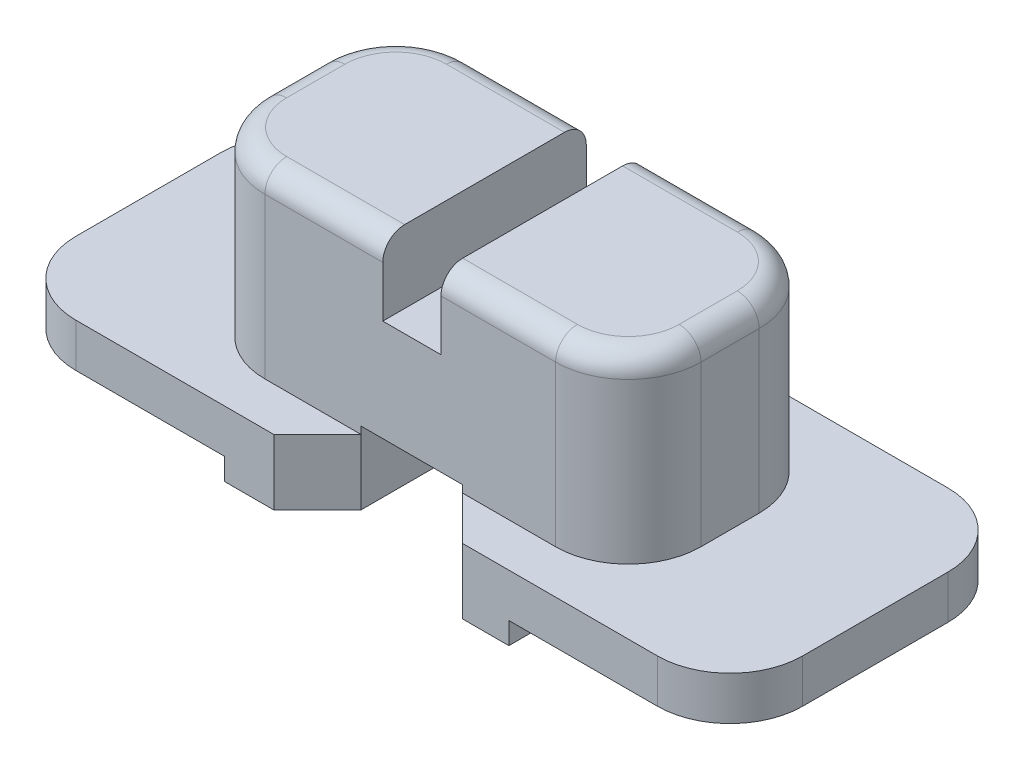
SolidWorks part; units mm, degrees
ref_plane "前视基准面" through (0, 0, 0) normal (0, 0, 1) x (1, 0, 0)
ref_plane "上视基准面" through (0, 0, 0) normal (0, 1, 0) x (1, 0, 0)
ref_plane "右视基准面" through (0, 0, 0) normal (1, 0, 0) x (0, 0, -1)
sketch "草图1" plane through (0, 0, 0) normal (0, 1, 0) x (1, 0, 0)
  line L1 (-4.5475, 2) -> (5.4525, 2)
  line L2 (-4.5475, 2) -> (-4.5475, -2)
  line L3 (-4.5475, -2) -> (5.4525, -2)
  line L4 (5.4525, 2) -> (5.4525, -2)
  line L5 (-4.5475, 2) -> (5.4525, -2) construction
  line L6 (-4.5475, -2) -> (5.4525, 2) construction
  point P0 (0.4525, 0)
  point P5 (0, 0)
  point P6 (0, 0)
  point P7 (0.4525, 0)
  dimension "D1" = 10
  dimension "D2" = 4
extrude "凸台-拉伸1" add sketch "草图1" along normal blind 0.6
sketch "草图2" plane through (0, 0.6, 0) normal (0, 1, 0) x (1, 0, 0)
  line L1 (-2.5475, 1.4) -> (3.4525, 1.4)
  line L2 (-2.5475, 1.4) -> (-2.5475, -1.4)
  line L3 (-2.5475, -1.4) -> (3.4525, -1.4)
  line L4 (3.4525, 1.4) -> (3.4525, -1.4)
  line L5 (-2.5475, 1.4) -> (3.4525, -1.4) construction
  line L6 (-2.5475, -1.4) -> (3.4525, 1.4) construction
  line L7 (5.4525, -2) -> (5.4525, 2) construction
  point P0 (0.4525, 0)
  point P5 (0.4525, 0)
  point P6 (0, 0)
  point P12 (5.4525, 0)
  dimension "D1" = 2.8
  dimension "D2" = 6
extrude "凸台-拉伸2" add sketch "草图2" along normal blind 2.5
fillet "圆角1" radius 1 8 edges at (-4.5475, 0.3, 2) (-2.5475, 1.85, 1.4) (5.4525, 0.3, 2) (3.4525, 1.85, 1.4) (-2.5475, 1.85, -1.4) (3.4525, 1.85, -1.4) (5.4525, 0.3, -2) (-4.5475, 0.3, -2)
sketch "草图7" plane through (0, 0, 1.4) normal (0, 0, 1) x (1, 0, 0)
  line L0 (-1.5475, 3.1) -> (2.4525, 3.1) construction
  line L1 (0.8748, 2.1) -> (0.0748, 2.1)
  line L2 (0.8748, 2.1) -> (0.8748, 3.1)
  line L3 (0.8748, 3.1) -> (0.0748, 3.1)
  line L4 (0.0748, 2.1) -> (0.0748, 3.1)
  line L5 (0.8748, 2.1) -> (0.0748, 3.1) construction
  line L6 (0.8748, 3.1) -> (0.0748, 2.1) construction
  point P0 (0.4748, 2.6)
  dimension "D1" = 0.8
extrude "切除-拉伸2" cut sketch "草图7" against normal up to next and the other way through all
sketch "草图8" plane through (0, 0, 0) normal (0, -1, 0) x (1, 0, 0)
  line L0 (-3.5475, 2) -> (4.4525, 2) construction
  line L1 (-1.5043, 2) -> (2.4092, 2)
  line L2 (-1.5043, 2) -> (-1.5043, -2)
  line L3 (-1.5043, -2) -> (2.4092, -2)
  line L4 (2.4092, 2) -> (2.4092, -2)
  line L5 (-1.5043, 2) -> (2.4092, -2) construction
  line L6 (-1.5043, -2) -> (2.4092, 2) construction
  line L7 (4.4525, -2) -> (-3.5475, -2) construction
  point P0 (0.4525, 0)
  point P7 (0.4525, 2)
extrude "凸台-拉伸3" add sketch "草图8" along normal blind 0.3
sketch "草图9" plane through (0, 0, -2) normal (0, 0, -1) x (-1, 0, 0)
  line L0 (1.5043, -0.3) -> (-2.4092, -0.3) construction
  line L1 (-1.1748, -0.3) -> (0.2252, -0.3)
  line L2 (-1.1748, -0.3) -> (-1.1748, 0.7)
  line L3 (-1.1748, 0.7) -> (0.2252, 0.7)
  line L4 (0.2252, -0.3) -> (0.2252, 0.7)
  line L5 (-0.0748, 2.1) -> (-0.8748, 2.1) construction
  point P6 (-0.4748, 0.7)
  point P9 (-0.4748, 2.1)
  dimension "D1" = 1.4
  dimension "D2" = 1
extrude "切除-拉伸3" cut sketch "草图9" against normal up to next
chamfer "倒角2" distance 0.6 angle 45 4 edges at (-0.2252, 0.15, 2) (-0.2252, 0.15, -2) (1.1748, 0.15, -2) (1.1748, 0.15, 2)
fillet "圆角2" radius 0.3 10 edges at (1.6636, 3.1, 1.4) (3.1596, 3.1, 1.1071) (3.4525, 3.1, 0) (1.6636, 3.1, -1.4) (-0.7364, 3.1, -1.4) (-0.7364, 3.1, 1.4) (-2.2546, 3.1, 1.1071) (-2.5475, 3.1, 0) (3.1596, 3.1, -1.1071) (-2.2546, 3.1, -1.1071)
